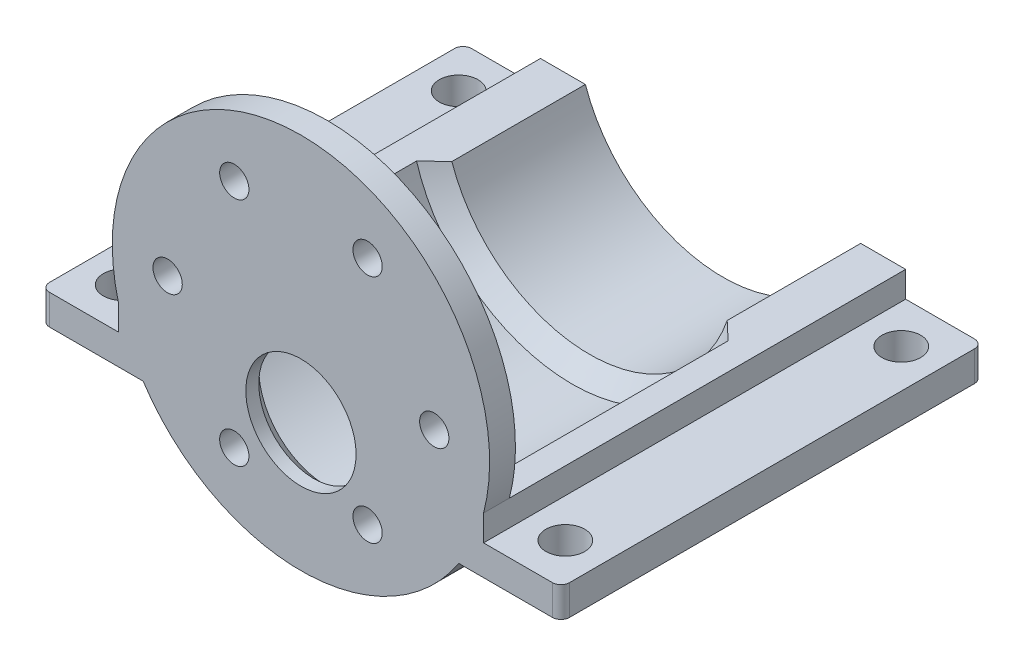
SolidWorks part; units mm, degrees
ref_plane "Front Plane" through (0, 0, 0) normal (0, 0, 1) x (1, 0, 0)
ref_plane "Top Plane" through (0, 0, 0) normal (0, 1, 0) x (1, 0, 0)
ref_plane "Right Plane" through (0, 0, 0) normal (1, 0, 0) x (0, 0, -1)
sketch "Sketch1" plane through (0, 0, 0) normal (0, 0, 1) x (1, 0, 0)
  line L0 (0, 0) -> (15.475, 0) construction
  line L1 (0, 0) -> (15.475, 0) construction
  line L2 (0, 0) -> (7.7375, -13.4017) construction
  line L3 (20.1832, -8.5) -> (30.1832, -8.5)
  line L4 (0, 0) -> (0, -7) construction
  line L5 (30.1832, -8.5) -> (30.1832, -12)
  line L6 (-20.1832, -8.5) -> (20.1832, -8.5)
  line L7 (30.1832, -12) -> (18.3197, -12)
  line L8 (-20.1832, -8.5) -> (-30.1832, -8.5)
  line L9 (-30.1832, -8.5) -> (-30.1832, -12)
  line L10 (-30.1832, -12) -> (-18.3197, -12)
  line L11 (-21.1981, -8.5) -> (-21.1981, -5.5)
  line L12 (-21.1981, -5.5) -> (-15.98, -5.5)
  line L13 (21.1981, -8.5) -> (21.1981, -5.5)
  line L14 (21.1981, -5.5) -> (15.98, -5.5)
  circle A0 centre (0, 0) radius 18.9
  circle A2 centre (0, 0) radius 16.9
  circle A4 centre (15.475, 0) radius 1.7
  circle A5 centre (7.7375, -13.4017) radius 1.7
  circle A6 centre (-7.7375, -13.4017) radius 1.7
  circle A7 centre (-15.475, 0) radius 1.7
  circle A8 centre (-7.7375, 13.4017) radius 1.7
  circle A9 centre (7.7375, 13.4017) radius 1.7
  circle A10 centre (0, 0) radius 21.9
  circle A11 centre (0, 0) radius 18.15
  circle A22 centre (0, -7) radius 6.4
  dimension "D1" = 37.8
  dimension "D2" = 33.8
  dimension "D3" = 3.4
  dimension "D7" = 43.8
  dimension "D8" = 36.3
  dimension "D12" = 12.8
  dimension "D4" = 6
  dimension "D5" = 60
  dimension "D6" = 15.475
  dimension "D13" = 1.5
  dimension "D14" = 7
  dimension "D16" = 3.5
  dimension "D17" = 10
  dimension "D18" = 3
extrude "Boss-Extrude1" add sketch "Sketch1" against normal blind 3 from offset 94 contours L6 A10 A0 | A11 L6 A0 | L6 A11 A2 A5 A6 | A22 L6 A2 A6 A5 | A22 L6 A2 A4 A9 A8 A7 | L12 A11 L6 A2 | A11 L12 A0 L6 | L12 A10 L6 A0 | L14 A10 L12 A0 | A11 L14 A0 L12 | L14 A11 L12 A2 A7 A8 A9 A4 | L6 A10 L14 A0 | A11 L6 A0 L14 | L6 A11 L14 A2 region at (18.9554, -10.0924, 0) region at (19.1257, -7.0145, 0) region at (0, -18.5467, 0) region at (17.1179, -7.018, 0) region at (19.6401, -4.9834, 0) region at (0, -17.8151, 0) region at (16.027, -7.0205, 0) region at (-17.1179, -7.018, 0) region at (-19.1257, -7.0145, 0) region at (17.6893, -5.0501, 0) region at (12.0472, -11.4146, 0) region at (0, 3.7482, 0) region at (-16.027, -7.0205, 0) region at (16.6383, -5.0668, 0)
extrude "Boss-Extrude2" add sketch "Sketch1<5>" against normal blind 27.5 from surface contours L6 A10 A0 | L12 A10 L6 A0 | L6 A10 L14 A0 region at (18.9554, -10.0924, 0) region at (19.1257, -7.0145, 0) region at (-19.1257, -7.0145, 0) starting at face at (-13.775, 0, 91)
sketch "Sketch1<5>" plane through (0, 0, 0) normal (0, 0, 1) x (1, 0, 0) same geometry as "Sketch1"
extrude "Boss-Extrude3" add sketch "Sketch1<6>" against normal blind 18.5 from surface contours L6 A10 A0 | A11 L6 A0 | L6 A11 A2 A5 A6 | A2 A6 | A2 A5 | L12 A10 L6 A0 | A11 L12 A0 L6 | L12 A11 L6 A2 | L6 A11 L14 A2 | A11 L6 A0 L14 | L6 A10 L14 A0 region at (18.9554, -10.0924, 0) region at (19.1257, -7.0145, 0) region at (0, -18.5467, 0) region at (17.1179, -7.018, 0) region at (0, -17.8151, 0) region at (16.027, -7.0205, 0) region at (-17.1179, -7.018, 0) region at (-19.1257, -7.0145, 0) region at (-16.027, -7.0205, 0) region at (8.5026, -14.727, 0) region at (-8.5026, -14.727, 0) starting at face at (0, -12.95, 63.5)
sketch "Sketch1<6>" plane through (0, 0, 0) normal (0, 0, 1) x (1, 0, 0) same geometry as "Sketch1"
extrude "Boss-Extrude7" add sketch "Sketch1<11>" along normal up to surface (94 mm away) from surface contours A10 L8 L9 L10 | A10 L8 | A10 L7 L5 L3 | A10 L3 L13 region at (20.8725, -7.5426, 0) region at (24.738, -10.2999, 0) region at (-24.738, -10.2999, 0) region at (-20.8725, -7.5426, 0) up to face at (-13.775, 0, 94) starting at face at (0, -12.45, 45)
sketch "Sketch1<11>" plane through (0, 0, 0) normal (0, 0, 1) x (1, 0, 0) same geometry as "Sketch1"
sketch "Sketch4" plane through (0, -8.5, 0) normal (0, 1, 0) x (1, 0, 0)
  line L0 (25.6906, -50) -> (25.6906, -89) construction
  line L5 (-25.6906, -50) -> (-25.6906, -89) construction
  line L6 (-30.1832, -94) -> (-30.1832, -45) construction
  line L7 (-30.1832, -45) -> (-21.1981, -45) construction
  line L8 (30.1832, -45) -> (21.1981, -45) construction
  line L9 (-25.6906, -50) -> (-25.6906, -45) construction
  line L10 (-25.6906, -89) -> (-25.6906, -94) construction
  line L11 (-30.1832, -94) -> (-21.1981, -94) construction
  circle A0 centre (-25.6906, -50) radius 2.25
  circle A1 centre (-25.6906, -89) radius 2.25
  circle A2 centre (25.6906, -50) radius 2.25
  circle A3 centre (25.6906, -89) radius 2.25
  point P8 (-25.6906, -69.5)
  point P11 (-30.1832, -69.5)
  point P12 (25.6906, -69.5)
  point P15 (-25.6906, -45)
  point P19 (25.6906, -45)
  dimension "D1" = 4.5
  dimension "D2" = 5
extrude "Cut-Extrude5" cut sketch "Sketch4" against normal through all both and the other way through all
chamfer "Chamfer3" distance 3 angle 45 1 edges at (0, -16.9, 63.5)
chamfer "Chamfer4" distance 1.5 angle 45 1 edges at (6.4, -7, 91)
fillet "Fillet2" radius 1 4 edges at (-30.1832, -10.25, 94) (30.1832, -10.25, 94) (-30.1832, -10.25, 45) (30.1832, -10.25, 45)
